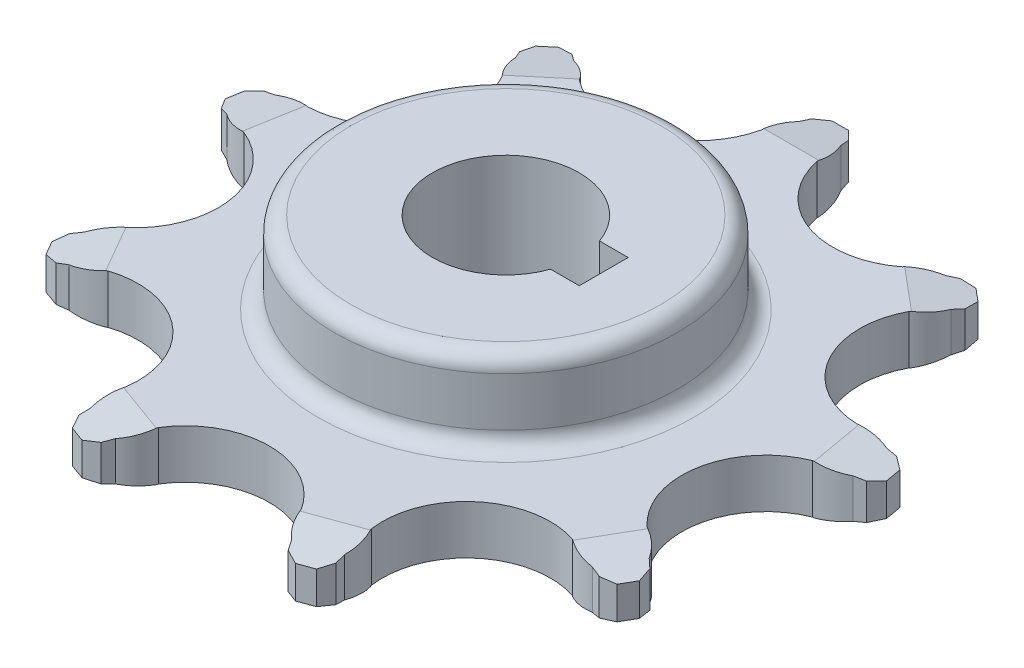
SolidWorks part; units mm, degrees
material "Cast Alloy Steel"
ref_plane "Front Plane" through (0, 0, 0) normal (0, 0, 1) x (1, 0, 0)
ref_plane "Top Plane" through (0, 0, 0) normal (0, 1, 0) x (1, 0, 0)
ref_plane "Right Plane" through (0, 0, 0) normal (1, 0, 0) x (0, 0, -1)
sketch "Sketch1" plane through (0, 0, 0) normal (0, 1, 0) x (1, 0, 0)
  line L0 (-1.1362, 19.8796) -> (-1.2724, 19.2593)
  line L1 (-1.1362, 19.8796) -> (-0.5, 20.5)
  line L2 (0, 20.5) -> (-0.5, 20.5)
  line L3 (0, 20.5) -> (0.5, 20.5)
  line L4 (1.1362, 19.8796) -> (0.5, 20.5)
  line L5 (1.1362, 19.8796) -> (1.2724, 19.2593)
  line L6 (11.908, 15.959) -> (11.4049, 15.5713)
  line L7 (11.908, 15.959) -> (12.7941, 16.0253)
  line L8 (13.1771, 15.7039) -> (12.7941, 16.0253)
  line L9 (13.1771, 15.7039) -> (13.5602, 15.3825)
  line L10 (13.6487, 14.4984) -> (13.5602, 15.3825)
  line L11 (13.6487, 14.4984) -> (13.3543, 13.9356)
  line L12 (19.3803, 4.571) -> (18.7457, 4.5974)
  line L13 (19.3803, 4.571) -> (20.1017, 4.0522)
  line L14 (20.1886, 3.5598) -> (20.1017, 4.0522)
  line L15 (20.1886, 3.5598) -> (20.2754, 3.0674)
  line L16 (19.7749, 2.3331) -> (20.2754, 3.0674)
  line L17 (19.7749, 2.3331) -> (19.1876, 2.0913)
  line L18 (17.7844, -8.9559) -> (17.3152, -8.5277)
  line L19 (17.7844, -8.9559) -> (18.0035, -9.817)
  line L20 (17.7535, -10.25) -> (18.0035, -9.817)
  line L21 (17.7535, -10.25) -> (17.5035, -10.683)
  line L22 (16.6482, -10.9238) -> (17.5035, -10.683)
  line L23 (16.6482, -10.9238) -> (16.0428, -10.7315)
  line L24 (7.8669, -18.2921) -> (7.7827, -17.6626)
  line L25 (7.8669, -18.2921) -> (7.4813, -19.0927)
  line L26 (7.0114, -19.2637) -> (7.4813, -19.0927)
  line L27 (7.0114, -19.2637) -> (6.5416, -19.4347)
  line L28 (5.7316, -19.0693) -> (6.5416, -19.4347)
  line L29 (5.7316, -19.0693) -> (5.3914, -18.533)
  line L30 (-5.7316, -19.0693) -> (-5.3914, -18.533)
  line L31 (-5.7316, -19.0693) -> (-6.5416, -19.4347)
  line L32 (-11.908, 15.959) -> (-12.7941, 16.0253)
  line L33 (-13.1771, 15.7039) -> (-12.7941, 16.0253)
  line L34 (-13.1771, 15.7039) -> (-13.5602, 15.3825)
  line L35 (-11.908, 15.959) -> (-11.4049, 15.5713)
  line L36 (-9.8999, 14.4115) -> (-9.8346, 14.3612)
  line L37 (-13.6487, 14.4984) -> (-13.5602, 15.3825)
  line L38 (-13.6487, 14.4984) -> (-13.3543, 13.9356)
  line L40 (-7.0114, -19.2637) -> (-6.5416, -19.4347)
  line L41 (-7.0114, -19.2637) -> (-7.4813, -19.0927)
  line L42 (-7.8669, -18.2921) -> (-7.4813, -19.0927)
  line L43 (-7.8669, -18.2921) -> (-7.7827, -17.6626)
  line L44 (-16.6482, -10.9238) -> (-16.0428, -10.7315)
  line L45 (-16.6482, -10.9238) -> (-17.5035, -10.683)
  line L46 (-17.7535, -10.25) -> (-17.5035, -10.683)
  line L47 (-17.7535, -10.25) -> (-18.0035, -9.817)
  line L48 (-17.7844, -8.9559) -> (-18.0035, -9.817)
  line L49 (-17.7844, -8.9559) -> (-17.3152, -8.5277)
  line L50 (-19.7749, 2.3331) -> (-19.1876, 2.0913)
  line L51 (-19.7749, 2.3331) -> (-20.2754, 3.0674)
  line L52 (-20.1886, 3.5598) -> (-20.2754, 3.0674)
  line L53 (-20.1886, 3.5598) -> (-20.1017, 4.0522)
  line L54 (-19.3803, 4.571) -> (-20.1017, 4.0522)
  line L55 (-19.3803, 4.571) -> (-18.7457, 4.5974)
  arc A3 (-1.6797, 17.4034) -> (-9.8999, 14.4115) centre (-6.7218, 18.468) cw
  arc A4 (-11.4049, 15.5713) -> (-9.8999, 14.4115) centre (-12.5208, 12.5669) cw
  arc A5 (-16.8473, 4.6763) -> (-12.4734, 12.252) centre (-17.0202, 9.8266) ccw
  arc A6 (-13.3543, 13.9356) -> (-12.4734, 12.252) centre (-10.2018, 14.5128) ccw
  arc A7 (-9.8999, 14.4115) -> (-1.6797, 17.4034) centre (-6.7218, 18.468) ccw
  arc A8 (-1.2724, 19.2593) -> (-1.6797, 17.4034) centre (1.5136, 17.675) ccw
  arc A9 (1.2724, 19.2593) -> (1.6797, 17.4034) centre (-1.5136, 17.675) cw
  arc A10 (9.8999, 14.4115) -> (1.6797, 17.4034) centre (6.7218, 18.468) cw
  arc A11 (1.6797, 17.4034) -> (9.8999, 14.4115) centre (6.7218, 18.468) ccw
  arc A12 (11.4049, 15.5713) -> (9.8999, 14.4115) centre (12.5208, 12.5669) ccw
  arc A13 (13.3543, 13.9356) -> (12.4734, 12.252) centre (10.2018, 14.5128) cw
  arc A14 (16.8473, 4.6763) -> (12.4734, 12.252) centre (17.0202, 9.8266) cw
  arc A15 (12.4734, 12.252) -> (16.8473, 4.6763) centre (17.0202, 9.8266) ccw
  arc A16 (18.7457, 4.5974) -> (16.8473, 4.6763) centre (17.6694, 1.5786) ccw
  arc A17 (19.1876, 2.0913) -> (17.4307, 1.3678) centre (17.1437, 4.5599) cw
  arc A18 (15.9116, -7.247) -> (17.4307, 1.3678) centre (19.3546, -3.4127) cw
  arc A19 (17.4307, 1.3678) -> (15.9116, -7.247) centre (19.3546, -3.4127) ccw
  arc A20 (17.3152, -8.5277) -> (15.9116, -7.247) centre (14.5502, -10.1484) ccw
  arc A21 (16.0428, -10.7315) -> (14.2319, -10.1564) centre (16.0638, -7.5267) cw
  arc A22 (7.5307, -15.7793) -> (14.2319, -10.1564) centre (12.6328, -15.0552) cw
  arc A23 (14.2319, -10.1564) -> (7.5307, -15.7793) centre (12.6328, -15.0552) ccw
  arc A24 (7.7827, -17.6626) -> (7.5307, -15.7793) centre (4.6229, -17.1268) ccw
  arc A25 (5.3914, -18.533) -> (4.3739, -16.9283) centre (7.4676, -16.0914) cw
  arc A26 (-4.3739, -16.9283) -> (4.3739, -16.9283) centre (0, -19.6532) cw
  arc A27 (4.3739, -16.9283) -> (-4.3739, -16.9283) centre (0, -19.6532) ccw
  arc A28 (-5.3914, -18.533) -> (-4.3739, -16.9283) centre (-7.4676, -16.0914) ccw
  arc A29 (-7.7827, -17.6626) -> (-7.5307, -15.7793) centre (-4.6229, -17.1268) cw
  arc A30 (-14.2319, -10.1564) -> (-7.5307, -15.7793) centre (-12.6328, -15.0552) cw
  arc A31 (-7.5307, -15.7793) -> (-14.2319, -10.1564) centre (-12.6328, -15.0552) ccw
  arc A32 (-16.0428, -10.7315) -> (-14.2319, -10.1564) centre (-16.0638, -7.5267) ccw
  arc A33 (-17.3152, -8.5277) -> (-15.9116, -7.247) centre (-14.5502, -10.1484) cw
  arc A34 (-17.4307, 1.3678) -> (-15.9116, -7.247) centre (-19.3546, -3.4127) cw
  arc A35 (-15.9116, -7.247) -> (-17.4307, 1.3678) centre (-19.3546, -3.4127) ccw
  arc A36 (-19.1876, 2.0913) -> (-17.4307, 1.3678) centre (-17.1437, 4.5599) ccw
  arc A37 (-18.7457, 4.5974) -> (-16.8473, 4.6763) centre (-17.6694, 1.5786) cw
  arc A38 (-12.4734, 12.252) -> (-16.8473, 4.6763) centre (-17.0202, 9.8266) cw
  point P145 (0, 0)
  dimension "D1" = 9
extrude "Boss-Extrude1" add sketch "Sketch1" along normal blind 3 contours A37 L55 L54 L53 L52 L51 L50 A36 A34 A33 L49 L48 L47 L46 L45 L44 A32 A30 A29 L43 L42 L41 L40 L31 L30 A28 A26 A25 L29 L28 L27 L26 L25 L24 A24 A22 A21 L23 L22 L21 L20 L19 L18 A20 A18 A17 L17 L16 L15 L14 L13 region at (0, 0, 0)
sketch "Sketch2" plane through (0, 3, 0) normal (0, 1, 0) x (1, 0, 0)
  circle A0 centre (0, 0) radius 10.5
extrude "Boss-Extrude2" add sketch "Sketch2" along normal blind 5
fillet "Fillet1" radius 1 1 edges at (0, 3, 10.5)
fillet "Fillet2" radius 1 1 edges at (0, 8, 10.5)
sketch "Sketch3" plane through (0, 8, 0) normal (0, 1, 0) x (1, 0, 0)
  line L1 (6, 0) -> (6, 1.5)
  line L2 (6, 0) -> (6, -1.5)
  line L3 (6, 1.5) -> (4.2426, 1.5)
  line L4 (6, -1.5) -> (4.2426, -1.5)
  arc A0 (4.2426, 1.5) -> (4.2426, -1.5) centre (0, 0) ccw
  dimension "D1" = 4.5
  dimension "D2" = 1.5
  dimension "D3" = 6
  dimension "D4" = 1.5
sketch "Sketch4" plane through (0, 0, 0) normal (0, -1, 0) x (1, 0, 0)
  circle A0 centre (0, 0) radius 10.5
extrude "Boss-Extrude3" add sketch "Sketch4" along normal blind 2
fillet "Fillet3" radius 1 1 edges at (0, 0, 10.5)
fillet "Fillet4" radius 1 1 edges at (0, -2, -10.5)
extrude "Cut-Extrude1" cut sketch "Sketch3" against normal up to surface (10 mm away) contours A0 L4 L2 L1 L3 up to face at (0, -2, -9.5)
chamfer "Chamfer1" distance 3 distance2 0.5 9 edges at (17.7535, 3, 10.25) (-17.7535, 3, 10.25) (-7.0114, 3, 19.2637) (7.0114, 3, 19.2637) (-20.1886, 3, -3.5598) (-13.1771, 3, -15.7039) (0, 3, -20.5) (13.1771, 3, -15.7039) (20.1886, 3, -3.5598) first distance on face at (0, 3, 11.5)
chamfer "Chamfer2" distance 0.5 distance2 3 9 edges at (17.7535, 0, 10.25) (7.0114, 0, 19.2637) (-7.0114, 0, 19.2637) (-17.7535, 0, 10.25) (-20.1886, 0, -3.5598) (-13.1771, 0, -15.7039) (0, 0, -20.5) (13.1771, 0, -15.7039) (20.1886, 0, -3.5598) first distance on face at (17.7535, 1.25, 10.25) first distance on face at (7.0114, 1.25, 19.2637) first distance on face at (-7.0114, 1.25, 19.2637) first distance on face at (-17.7535, 1.25, 10.25) first distance on face at (-20.1886, 1.25, -3.5598) first distance on face at (-13.1771, 1.25, -15.7039) first distance on face at (0, 1.25, -20.5) first distance on face at (13.1771, 1.25, -15.7039) first distance on face at (20.1886, 1.25, -3.5598)
